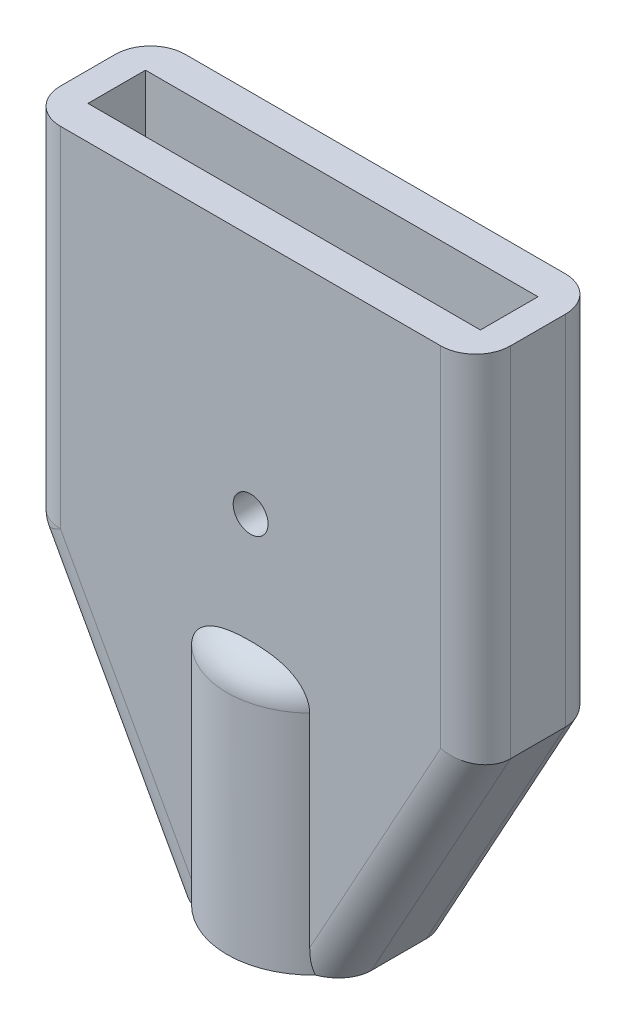
SolidWorks part; units mm, degrees
ref_plane "Front Plane" through (0, 0, 0) normal (0, 0, 1) x (1, 0, 0)
ref_plane "Top Plane" through (0, 0, 0) normal (0, 1, 0) x (1, 0, 0)
ref_plane "Right Plane" through (0, 0, 0) normal (1, 0, 0) x (0, 0, -1)
sketch "Sketch2" plane through (0, 0, 0) normal (0, 0, 1) x (1, 0, 0)
  line L0 (0, 0) -> (17.825, 0) construction
  line L1 (0, 0) -> (0, 51.1905) construction
  line L2 (12.9, 35) -> (12.9, 0) construction
  line L3 (7.975, 0) -> (17.825, 0)
  line L4 (0, 14.5) -> (0, 35)
  line L5 (0, 35) -> (25.8, 35)
  line L6 (25.8, 14.5) -> (25.8, 35)
  line L7 (0, 14.5) -> (25.8, 14.5) construction
  line L8 (7.975, 14.5) -> (7.975, 0) construction
  line L9 (17.825, 14.5) -> (17.825, 0) construction
  line L10 (17.825, 0) -> (25.8, 14.5)
  line L11 (0, 14.5) -> (7.975, 0)
  dimension "D1" = 25.8
  dimension "D2" = 35
  dimension "D3" = 14.5
  dimension "D4" = 4.925
  dimension "D5" = 4.925
  dimension "D6" = 9.85
extrude "Boss-Extrude1" add sketch "Sketch2" along normal blind 7.15
sketch "Sketch3" plane through (0, 0, 0) normal (0, -1, 0) x (1, 0, 0)
  line L0 (12.9, 7.15) -> (12.9, 0) construction
  line L1 (7.975, 7.15) -> (17.825, 7.15) construction
  line L2 (7.975, 0) -> (17.825, 0) construction
  line L3 (17.825, 3.575) -> (7.975, 3.575) construction
  line L4 (17.825, 7.15) -> (17.825, 0) construction
  line L5 (7.975, 7.15) -> (7.975, 0) construction
  circle A0 centre (12.9, 3.575) radius 4.925
  dimension "D1" = 9.85
extrude "Boss-Extrude2" add sketch "Sketch3" against normal blind 15
sketch "Sketch4" plane through (0, 0, 0) normal (0, -1, 0) x (1, 0, 0)
  line L0 (7.975, 3.575) -> (17.825, 3.575) construction
  line L1 (7.975, 7.15) -> (7.975, 0) construction
  line L2 (17.825, 7.15) -> (17.825, 0) construction
  line L3 (12.9, 3.575) -> (12.9, -1.35) construction
  line L4 (12.9, 3.575) -> (12.9, 8.5) construction
  arc A0 (9.5125, 0) -> (16.2875, 0) centre (12.9, 3.575) ccw construction
  arc A1 (16.2875, 7.15) -> (9.5125, 7.15) centre (12.9, 3.575) ccw construction
  circle A2 centre (12.9, 3.575) radius 2.925
  dimension "D1" = 5.85
extrude "Cut-Extrude1" cut sketch "Sketch4" against normal blind 13.5
sketch "Sketch5" plane through (0, 35, 0) normal (0, 1, 0) x (1, 0, 0)
  line L0 (0, -3.575) -> (25.8, -3.575) construction
  line L1 (0, -7.15) -> (0, 0) construction
  line L2 (25.8, -7.15) -> (25.8, 0) construction
  line L3 (12.9, 0) -> (12.9, -7.15) construction
  line L4 (16.2875, 0) -> (9.5125, 0) construction
  line L5 (25.8, -7.15) -> (0, -7.15) construction
  line L7 (1.65, -5.225) -> (24.15, -5.225)
  line L8 (1.65, -5.225) -> (1.65, -1.925)
  line L9 (1.65, -1.925) -> (24.15, -1.925)
  line L10 (24.15, -5.225) -> (24.15, -1.925)
  line L11 (1.65, -5.225) -> (24.15, -1.925) construction
  line L12 (1.65, -1.925) -> (24.15, -5.225) construction
  point P12 (12.9, -3.575)
  dimension "D1" = 3.3
  dimension "D2" = 22.5
extrude "Cut-Extrude2" cut sketch "Sketch5" against normal blind 18
fillet "Fillet2" radius 2 1 edges at (3.9875, 7.25, 0)
fillet "Fillet3" radius 2 5 edges at (0, 14.5, 4.575) (0, 15.7155, 0.5858) (0, 24.75, 7.15) (0, 26.825, 0) (3.9875, 7.25, 7.15)
fillet "Fillet4" radius 2 4 edges at (25.8, 24.75, 7.15) (25.8, 24.75, 0) (21.8125, 7.25, 0) (21.8125, 7.25, 7.15)
fillet "Fillet5" radius 2 2 edges at (12.9, 15, 8.5) (12.9, 15, -1.35)
sketch "Sketch6" plane through (0, 0, 0) normal (0, 0, -1) x (-1, 0, 0)
  line L0 (-12.9, 35) -> (-12.9, 13) construction
  line L1 (-23.8, 35) -> (-2, 35) construction
  line L2 (-9.5125, 13) -> (-16.2875, 13) construction
  line L3 (-23.8, 21.1962) -> (-2, 21.1962) construction
  line L4 (-23.8, 35) -> (-23.8, 15.0137) construction
  line L5 (-2, 15.0137) -> (-2, 35) construction
  circle A0 centre (-12.9, 21.1962) radius 1
  dimension "D1" = 2
extrude "Cut-Extrude3" cut sketch "Sketch6" against normal through all both and the other way through all contours A0
